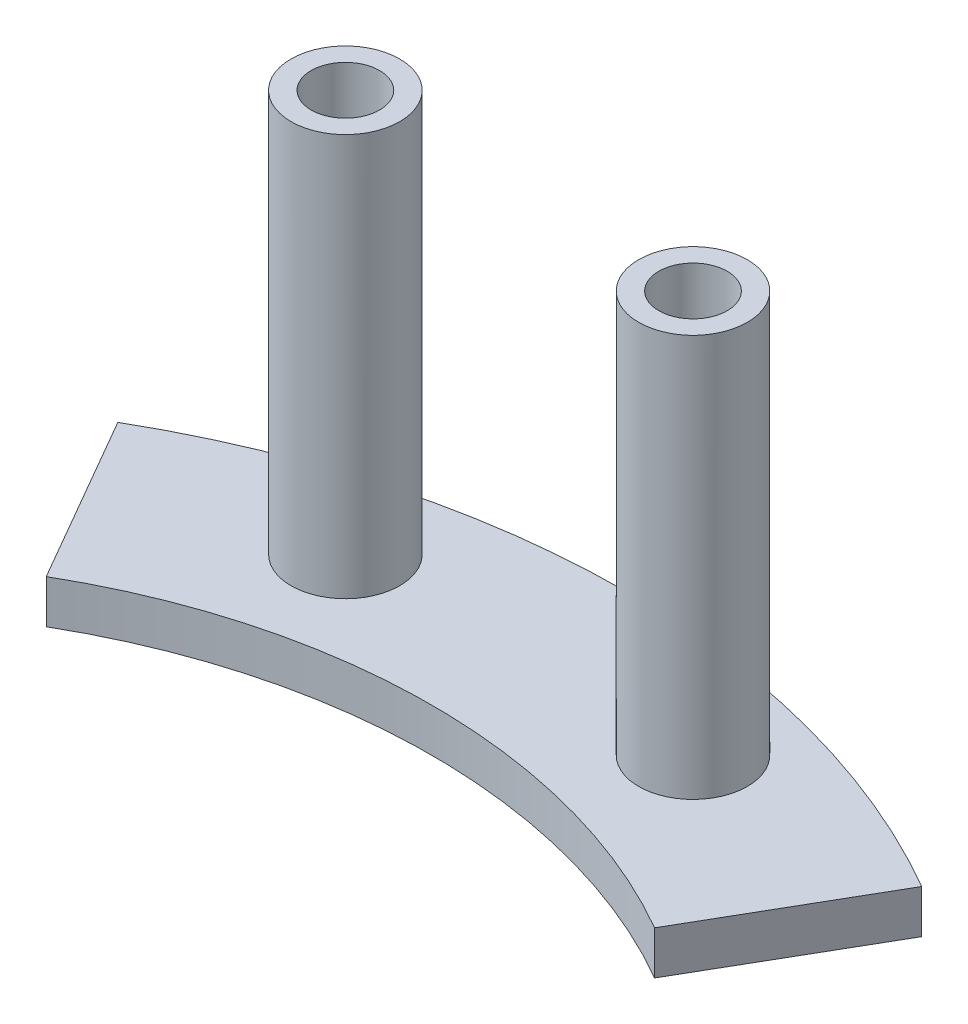
SolidWorks part; units mm, degrees
ref_plane "Front Plane" through (0, 0, 0) normal (0, 0, 1) x (1, 0, 0)
ref_plane "Top Plane" through (0, 0, 0) normal (0, 1, 0) x (1, 0, 0)
ref_plane "Right Plane" through (0, 0, 0) normal (1, 0, 0) x (0, 0, -1)
sketch "Sketch1" plane through (0, 0, 0) normal (0, 1, 0) x (1, 0, 0)
  line L0 (-14, 24.2487) -> (-18.5, 32.0429) construction
  line L1 (14, 24.2487) -> (18.5, 32.0429) construction
  line L2 (0, 0) -> (4, 0) construction
  line L3 (-18.5, 32.0429) -> (-14, 24.2487)
  line L4 (18.5, 32.0429) -> (14, 24.2487)
  circle A0 centre (0, 0) radius 28 construction
  circle A1 centre (0, 0) radius 37 construction
  arc A2 (-18.5, 32.0429) -> (18.5, 32.0429) centre (0, 0) cw
  arc A3 (-14, 24.2487) -> (14, 24.2487) centre (0, 0) cw
  arc A4 (-16.25, 28.1458) -> (16.25, 28.1458) centre (0, 0) cw construction
  dimension "D1" = 28
  dimension "D2" = 37
  dimension "D6" = 60
  dimension "D3" = 60
extrude "Boss-Extrude1" add sketch "Sketch1" along normal blind 2
sketch "Sketch2" plane through (0, 2, 0) normal (0, 1, 0) x (1, 0, 0)
  line L1 (14, 24.2487) -> (18.5, 32.0429) construction
  line L2 (-8, 32.0156) -> (8, 32.0156) construction
  line L3 (0, 32.0156) -> (0, 0) construction
  line L5 (-18.5, 32.0429) -> (-14, 24.2487) construction
  arc A0 (-16.5, 28.5788) -> (16.5, 28.5788) centre (0, 0) cw construction
  circle A1 centre (-8, 32.0156) radius 2.5
  circle A2 centre (8, 32.0156) radius 2.5
  dimension "D1" = 5
  dimension "D4" = 33
  dimension "D2" = 8
  dimension "D3" = 32.0156
extrude "Boss-Extrude2" add sketch "Sketch2" along normal blind 18.5
sketch "Sketch5" plane through (0, 20.5, 0) normal (0, 1, 0) x (1, 0, 0)
  circle A0 centre (-8, 32.0156) radius 1.575
  circle A2 centre (8, 32.0156) radius 1.575
  dimension "D1" = 3.15
extrude "Cut-Extrude1" cut sketch "Sketch5" against normal blind 3.5
